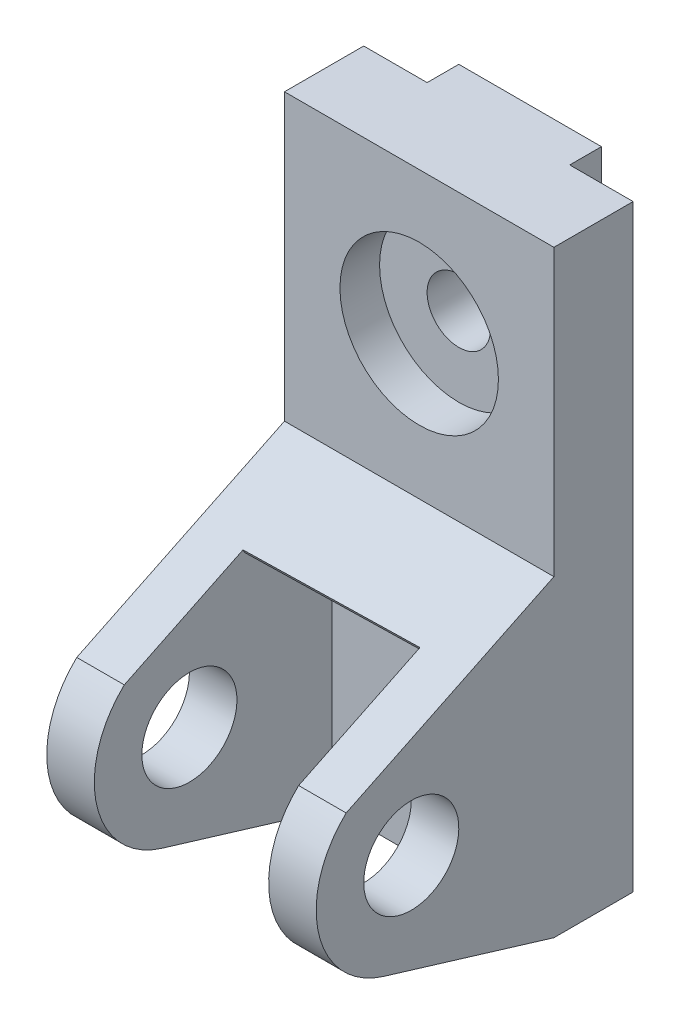
SolidWorks part; units mm, degrees
note: The reader was unsure of these and kept them because the rebuilt part matched: shared geometry of "Sketch1<3>", "Sketch1<5>", "Sketch1<6>".
ref_plane "Front Plane" through (0, 0, 0) normal (0, 0, 1) x (1, 0, 0)
ref_plane "Top Plane" through (0, 0, 0) normal (0, 1, 0) x (1, 0, 0)
ref_plane "Right Plane" through (0, 0, 0) normal (1, 0, 0) x (0, 0, -1)
sketch "Sketch1" plane through (0, 0, 0) normal (0, 0, 1) x (1, 0, 0)
  line L0 (-50.1524, -45.1454) -> (-50.1524, 44.8546)
  line L1 (-50.1524, 44.8546) -> (34.8476, 44.8546)
  line L2 (34.8476, 44.8546) -> (34.8476, -45.1454)
  line L3 (34.8476, -45.1454) -> (-50.1524, -45.1454)
  circle A0 centre (-7.6524, 0) radius 25
  circle A1 centre (-7.6524, 0) radius 10
  dimension "D3" = 50
  dimension "D4" = 20
  dimension "D1" = 85
  dimension "D2" = 90
extrude "Boss-Extrude1" add sketch "Sketch1" against normal blind 25 contours L3 L2 L1 L0 A0
extrude "Boss-Extrude2" add sketch "Sketch1<3>" against normal blind 25 separate body contours A0 A1 | A1
sketch "Sketch1<3>" plane through (0, 0, 0) normal (0, 0, 1) x (1, 0, 0) same geometry as "Sketch1"
extrude "Cut-Extrude1" cut sketch "Sketch1<5>" against normal through all contours A1
sketch "Sketch1<5>" plane through (0, 0, 0) normal (0, 0, 1) x (1, 0, 0) same geometry as "Sketch1"
extrude "Cut-Extrude2" cut sketch "Sketch1<6>" against normal blind 12.5 contours A0 A1
sketch "Sketch1<6>" plane through (0, 0, 0) normal (0, 0, 1) x (1, 0, 0) same geometry as "Sketch1"
sketch "Sketch3" plane through (34.8476, 0, 0) normal (1, 0, 0) x (0, 0, -1)
  line L0 (0, -45.1454) -> (-65.5403, -76.9373)
  line L1 (-53.7083, -127.511) -> (0, -143.8028)
  line L2 (0, -45.1454) -> (0, -143.8028)
  line L3 (0, -45.1454) -> (25, -45.1454)
  line L4 (25, -45.1454) -> (25, -143.8028)
  line L5 (25, -143.8028) -> (0, -143.8028)
  arc A2 (-49.4568, -69.1357) -> (-53.7083, -127.511) centre (-45, -98.8028) ccw
  circle A3 centre (-45, -98.8028) radius 15
  line M5 (0, -45.1454) -> (25, -45.1454)
  dimension "D1" = 60
  dimension "D2" = 30
  dimension "D3" = 45
  dimension "D4" = 70
extrude "Boss-Extrude3" add sketch "Sketch3" against normal blind 15 contours L0 A2 L1 L2 A3 | L5 L4 L2 M5
ref_plane "Plane1" through (-7.6524, 0, 0) normal (1, 0, 0) x (0, 0, -1)
mirror "Mirror1" about plane through (-7.6524, 0, 0) normal (1, 0, 0) of bodies 105
sketch "Sketch5" plane through (-50.1524, 0, 0) normal (-1, 0, 0) x (0, 0, 1)
  line L0 (0, -45.1454) -> (0, -143.8028)
  line L1 (0, -143.8028) -> (-25, -143.8028)
  line L2 (-25, -143.8028) -> (-25, -45.1454)
  line L3 (-25, -45.1454) -> (0, -45.1454)
extrude "Cut-Extrude3" cut sketch "Sketch5" against normal blind 15
sketch "Sketch7" plane through (34.8476, 0, 0) normal (1, 0, 0) x (0, 0, -1)
  line L0 (-27.0439, -58.2637) -> (0, -45.1454)
  line L1 (0, -45.1454) -> (-65.5403, -76.9373) construction
sketch "Sketch8" plane through (0, -45.1454, 0) normal (0, -1, 0) x (1, 0, 0)
  line L0 (-50.1524, -25) -> (-50.1524, 0)
  line L1 (-50.1524, -25) -> (-50.1524, 0) construction
  line L2 (-50.1524, 0) -> (34.8476, 0)
  line L3 (34.8476, 0) -> (34.8476, -25)
  line L4 (34.8476, -25) -> (-50.1524, -25)
extrude "Boss-Extrude8" add sketch "Sketch8" along normal blind 98
sketch "Sketch9" plane through (0, -36.5462, -17.7276) normal (0, 0.8997, 0.4364) x (1, 0, 0)
  line L0 (-50.1524, -51.1745) -> (34.8476, -49.7608)
  line L1 (-50.1524, -19.7032) -> (-50.1524, -92.5472) construction
  line L2 (34.8476, -49.7608) -> (34.8476, -19.7032) construction
  line L3 (34.8476, -49.7608) -> (34.8476, -19.7032)
  line L4 (34.8476, -19.7032) -> (-50.1524, -19.7032)
  line L5 (-50.1524, -19.7032) -> (-50.1524, -51.1745)
extrude "Boss-Extrude9" add sketch "Sketch9" against normal blind 1
sketch "Sketch12" plane through (0, 44.8546, 0) normal (0, 1, 0) x (1, 0, 0)
  line L0 (-30.1524, 25) -> (-30.1524, 35)
  line L1 (-50.1524, 25) -> (34.8476, 25) construction
  line L2 (-30.1524, 35) -> (14.8476, 35)
  line L3 (14.8476, 35) -> (14.8476, 25)
  line L4 (14.8476, 25) -> (-30.1524, 25)
  line L5 (-35.1524, 0) -> (19.8476, 0) construction
  point P9 (-7.6524, 0)
  point P10 (-7.6524, 25)
  dimension "D1" = 45
  dimension "D2" = 10
extrude "Boss-Extrude11" add sketch "Sketch12" against normal blind 188
sketch "Sketch11" plane through (19.8476, 0, 0) normal (1, 0, 0) x (0, 0, -1)
  line L0 (0, -143.8028) -> (-26.8541, -135.6569)
  line L1 (-53.7083, -127.511) -> (0, -143.8028) construction
  line L2 (-26.8541, -135.6569) -> (-27, -143.8028)
  line L3 (-27, -143.8028) -> (0, -143.8028)
extrude "Cut-Extrude4" cut sketch "Sketch11" against normal through all
